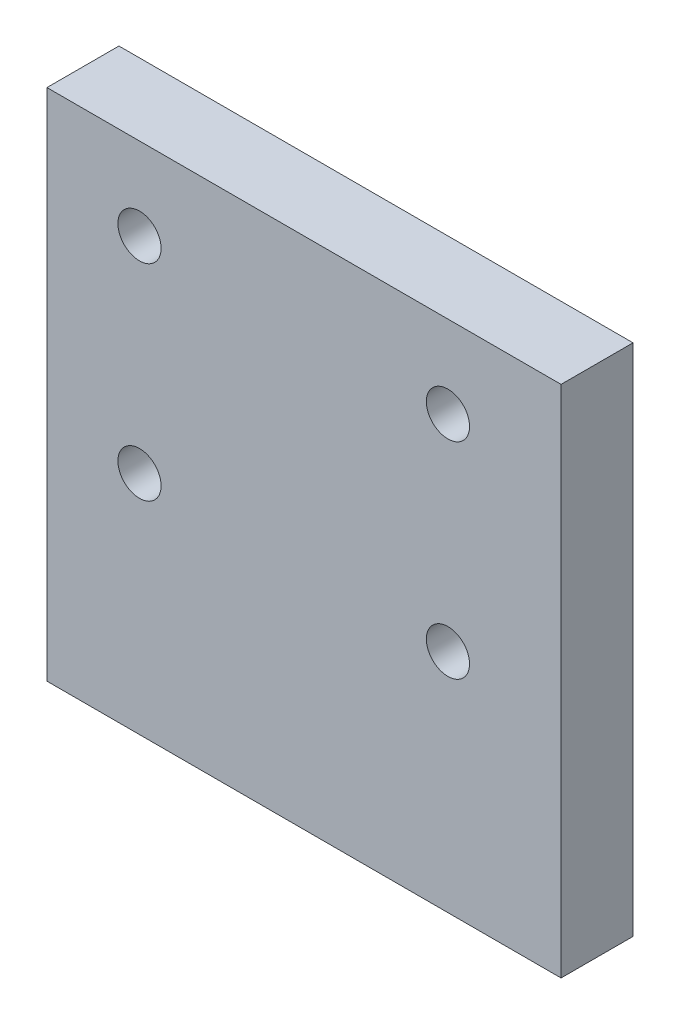
SolidWorks part; units mm, degrees
ref_plane "정면" through (0, 0, 0) normal (0, 0, 1) x (1, 0, 0)
ref_plane "윗면" through (0, 0, 0) normal (0, 1, 0) x (1, 0, 0)
ref_plane "우측면" through (0, 0, 0) normal (1, 0, 0) x (0, 0, -1)
sketch "스케치1" plane through (0, 0, 0) normal (0, 0, 1) x (1, 0, 0)
  line L1 (-25, 25) -> (25, 25)
  line L2 (-25, 25) -> (-25, -25)
  line L3 (-25, -25) -> (25, -25)
  line L4 (25, 25) -> (25, -25)
  line L5 (-25, 25) -> (25, -25) construction
  line L6 (-25, -25) -> (25, 25) construction
  point P0 (0, 0)
  dimension "D1" = 50
  dimension "D2" = 50
extrude "보스-돌출1" add sketch "스케치1" along normal blind 7
sketch "스케치2" plane through (0, 0, 7) normal (0, 0, 1) x (1, 0, 0)
  line L0 (-25, -25) -> (25, -25) construction
  line L1 (-25, 25) -> (-25, -25) construction
  circle A0 centre (-16, -3) radius 2.1
  circle A1 centre (14, -3) radius 2.1
  circle A2 centre (-16, 17) radius 2.1
  circle A3 centre (14, 17) radius 2.1
  dimension "D7" = 4.2
  dimension "D8" = 4.2
  dimension "D9" = 4.2
  dimension "D10" = 4.2
  dimension "D1" = 22
  dimension "D2" = 20
  dimension "D3" = 22
  dimension "D4" = 20
  dimension "D5" = 30
  dimension "D6" = 30
  dimension "D11" = 9
extrude "컷-돌출1" cut sketch "스케치2" against normal blind 7
